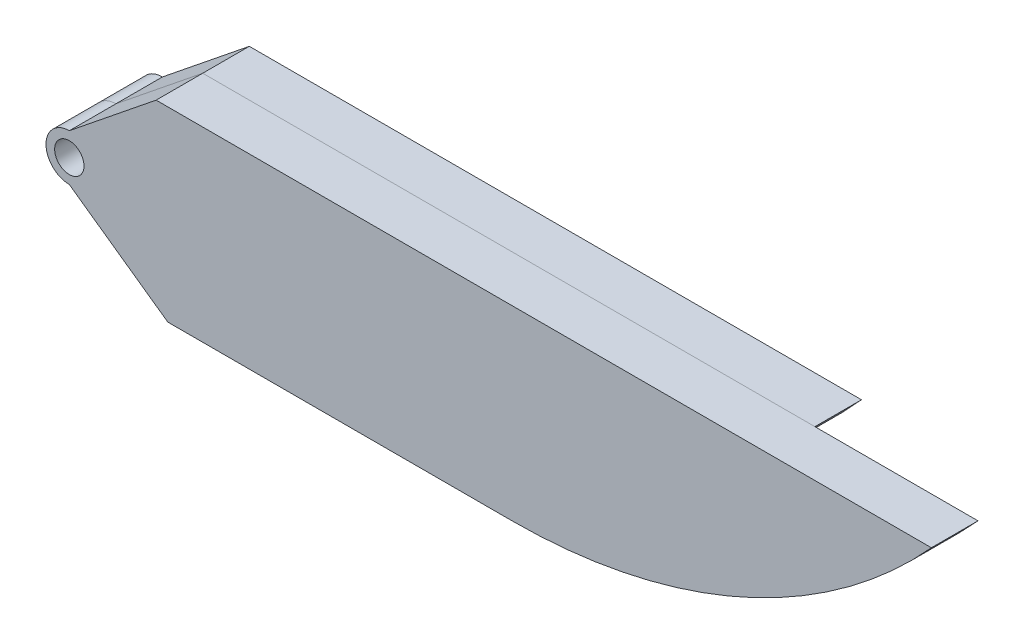
SolidWorks part; units mm, degrees
ref_plane "Front Plane" through (0, 0, 0) normal (0, 0, 1) x (1, 0, 0)
ref_plane "Top Plane" through (0, 0, 0) normal (0, 1, 0) x (1, 0, 0)
ref_plane "Right Plane" through (0, 0, 0) normal (1, 0, 0) x (0, 0, -1)
sketch "Sketch1" plane through (0, 0, 0) normal (0, 0, 1) x (1, 0, 0)
  line L1 (101.6, 25.4) -> (-101.6, 25.4)
  line L2 (101.6, 25.4) -> (101.6, -25.4)
  line L3 (101.6, -25.4) -> (-101.6, -25.4)
  line L4 (-101.6, 25.4) -> (-101.6, -25.4)
  line L5 (101.6, 25.4) -> (-101.6, -25.4) construction
  line L6 (101.6, -25.4) -> (-101.6, 25.4) construction
  point P0 (0, 0)
  dimension "D1" = 203.2
  dimension "D2" = 50.8
extrude "Boss-Extrude1" add sketch "Sketch1" along normal blind 12.7
sketch "Sketch3" plane through (0, 0, 12.7) normal (0, 0, 1) x (1, 0, 0)
  line L0 (0, 0) -> (-101.6, 0) construction
  line L1 (-101.6, 25.4) -> (-101.6, -25.4) construction
  circle A0 centre (-88.9, 0) radius 4
  dimension "D2" = 8
  dimension "D1" = 12.7
extrude "Cut-Extrude1" cut sketch "Sketch3" against normal through all
sketch "Sketch5" plane through (0, 0, 12.7) normal (0, 0, 1) x (1, 0, 0)
  line L0 (-101.6, -25.4) -> (101.6, -25.4) construction
  line L1 (-88.9, -6.35) -> (-62.0461, -25.4)
  line L2 (-88.9, 6.35) -> (-65.2393, 25.4)
  line L3 (101.6, 25.4) -> (-101.6, 25.4) construction
  line L4 (-65.2393, 25.4) -> (-101.6, 25.4)
  line L5 (-101.6, 25.4) -> (-101.6, -25.4)
  line L6 (-101.6, -25.4) -> (-62.0461, -25.4)
  line L7 (101.6, 25.4) -> (101.6, -25.4)
  line L8 (101.6, -25.4) -> (0, -25.4)
  arc A0 (0, -25.4) -> (101.6, 25.4) centre (-12.4455, 126.491) ccw
  arc A2 (-88.9, 6.35) -> (-88.9, -6.35) centre (-88.9, 0) ccw
  dimension "D1" = 152.4
  dimension "D2" = 12.7
extrude "Cut-Extrude2" cut sketch "Sketch5" against normal through all
sketch "Sketch6" plane through (0, 0, 12.7) normal (0, 0, 1) x (1, 0, 0)
  line L0 (-88.9, 0) -> (72.5592, 0) construction
  arc A0 (0, -25.4) -> (101.6, 25.4) centre (-12.4455, 126.491) ccw construction
  circle A1 centre (38.1, 0) radius 3.1347
  dimension "D1" = 127
sketch "Sketch7" plane through (0, 0, 0) normal (0, 0, -1) x (-1, 0, 0)
  line L0 (44.0204, -2.9977) -> (44.0204, 16.0523) construction
  point P3 (44.0204, -2.9977)
  point P4 (44.0204, 16.0523)
  dimension "D1" = 19.05
sketch "Sketch11" plane through (0, 0, 12.7) normal (0, 0, 1) x (1, 0, 0)
  line L0 (-65.2393, 25.4) -> (-88.9, 6.35)
  line L1 (-88.9, -6.35) -> (-62.0461, -25.4)
  line L2 (-62.0461, -25.4) -> (0, -25.4)
  line L3 (-65.2393, 25.4) -> (101.6, 25.4)
  line L4 (101.6, 25.4) -> (146.05, 25.4)
  line L5 (0, -25.4) -> (31.75, -25.4)
  arc A0 (-88.9, 6.35) -> (-88.9, -6.35) centre (-88.9, 0) ccw
  circle A1 centre (-88.9, 0) radius 4
  arc A3 (31.75, -25.4) -> (146.05, 25.4) centre (31.75, 128.5875) ccw
  point P9 (-95.25, 0)
  dimension "D1" = 44.45
  dimension "D2" = 31.75
extrude "Boss-Extrude4" add sketch "Sketch11" along normal blind 12.7 separate body contours L3 L4 A3 L5 L2 L1 A0 L0
extrude "Cut-Extrude4" cut sketch "Sketch11<5>" along normal blind 12.7 contours A1
sketch "Sketch11<5>" plane through (0, 0, 12.7) normal (0, 0, 1) x (1, 0, 0) same geometry as "Sketch11"
sketch "Sketch15" plane through (0, 0, 25.4) normal (0, 0, 1) x (1, 0, 0)
  arc A0 (-88.9, 6.35) -> (-88.9, -6.35) centre (-88.9, 0) ccw construction
  point P0 (-95.25, 0)
  point P1 (146.05, 25.4)
sketch "Sketch16" plane through (0, 0, 25.4) normal (0, 0, 1) x (1, 0, 0)
  point P0 (-95.25, 0)
  point P1 (146.05, 25.4)
sketch "Sketch17" plane through (0, 0, 25.4) normal (0, 0, 1) x (1, 0, 0)
  point P1 (146.05, 25.4)
  point P2 (-95.25, 0)
